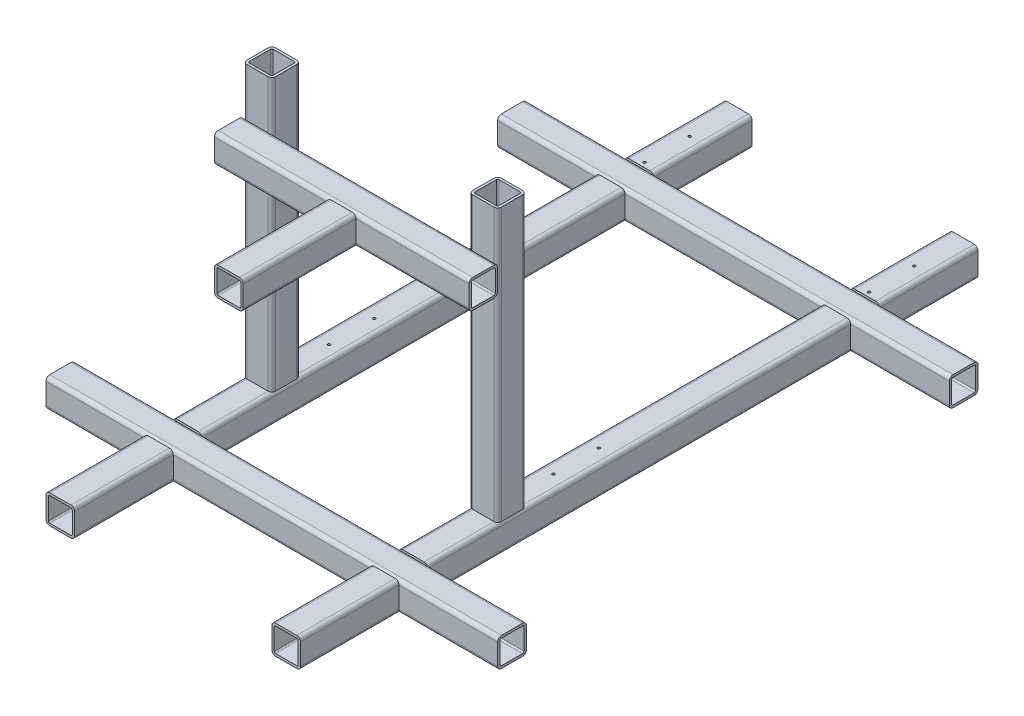
SolidWorks part; units mm, degrees
ref_plane "Front Plane" through (0, 0, 0) normal (0, 0, 1) x (1, 0, 0)
ref_plane "Top Plane" through (0, 0, 0) normal (0, 1, 0) x (1, 0, 0)
ref_plane "Right Plane" through (0, 0, 0) normal (1, 0, 0) x (0, 0, -1)
ref_plane "Bottom Face" through (0, 0, 0) normal (0, 1, 0) x (1, 0, 0)
ref_plane "Top Face" through (0, 38.1, 0) normal (0, 1, 0) x (1, 0, 0)
ref_plane "Mid Plane" through (0, 19.05, 0) normal (0, 1, 0) x (1, 0, 0)
ref_plane "Front Face" through (0, 0, 450) normal (0, 0, 1) x (1, 0, 0)
ref_plane "Back Face" through (0, 0, -450) normal (0, 0, 1) x (1, 0, 0)
ref_plane "Left Face" through (300, 0, 0) normal (1, 0, 0) x (0, 0, -1)
ref_plane "Right Face" through (-300, 0, 0) normal (1, 0, 0) x (0, 0, -1)
ref_plane "Divider Plane" through (0, 0, 150) normal (0, 0, 1) x (1, 0, 0)
ref_plane "Max Height Plane" through (0, 400, 0) normal (0, 1, 0) x (1, 0, 0)
ref_plane "Electronics Box Plane" through (0, 338.1, 0) normal (0, 1, 0) x (1, 0, 0)
sketch "Sketch2" plane through (300, 0, 0) normal (1, 0, 0) x (0, 0, -1)
  line L0 (330, 38.1) -> (-330, 38.1) construction
  line L5 (330, 0) -> (-330, 0) construction
  line L6 (0, 220) -> (0, -220) construction
  line L7 (-314.05, 38.1) -> (-285.95, 38.1)
  line L8 (-280.95, 33.1) -> (-280.95, 5)
  line L9 (-315.875, 33.1) -> (-315.875, 5)
  line L10 (-314.05, 3.175) -> (-285.95, 3.175)
  line L11 (-285.95, 0) -> (-314.05, 0)
  line L12 (-319.05, 5) -> (-319.05, 33.1)
  line L13 (-300, 38.1) -> (-300, 0) construction
  line L14 (-319.05, 19.05) -> (-280.95, 19.05) construction
  line L15 (-284.125, 5) -> (-284.125, 33.1)
  line L16 (-285.95, 34.925) -> (-314.05, 34.925)
  line L17 (-300, 34.925) -> (-300, 3.175) construction
  line L18 (-315.875, 19.05) -> (-284.125, 19.05) construction
  arc A0 (-285.95, 38.1) -> (-280.95, 33.1) centre (-285.95, 33.1) cw
  arc A1 (-280.95, 5) -> (-285.95, 0) centre (-285.95, 5) cw
  arc A2 (-314.05, 0) -> (-319.05, 5) centre (-314.05, 5) cw
  arc A3 (-319.05, 33.1) -> (-314.05, 38.1) centre (-314.05, 33.1) cw
  arc A4 (-315.875, 5) -> (-314.05, 3.175) centre (-314.05, 5) ccw
  arc A5 (-285.95, 3.175) -> (-284.125, 5) centre (-285.95, 5) ccw
  arc A6 (-284.125, 33.1) -> (-285.95, 34.925) centre (-285.95, 33.1) ccw
  arc A7 (-314.05, 34.925) -> (-315.875, 33.1) centre (-314.05, 33.1) ccw
  point P20 (-300, 19.05)
  point P39 (-300, 19.05)
  dimension "D1" = 5
  dimension "D2" = 300
  dimension "D3" = 3.175
extrude "Front Cross-Car Member" add sketch "Sketch2" against normal up to surface (600 mm away) up to plane "Right Face"
sketch "Sketch5" plane through (300, 0, 0) normal (1, 0, 0) x (0, 0, -1)
  line L0 (285.95, 38.1) -> (314.05, 38.1)
  line L1 (319.05, 33.1) -> (319.05, 5)
  line L2 (314.05, 0) -> (285.95, 0)
  line L3 (280.95, 5) -> (280.95, 33.1)
  line L4 (300, 38.1) -> (300, 0) construction
  line L5 (280.95, 19.05) -> (319.05, 19.05) construction
  line L6 (285.95, 34.925) -> (314.05, 34.925)
  line L7 (315.875, 33.1) -> (315.875, 5)
  line L8 (314.05, 3.175) -> (285.95, 3.175)
  line L9 (284.125, 5) -> (284.125, 33.1)
  line L10 (300, 34.925) -> (300, 3.175) construction
  line L11 (284.125, 19.05) -> (315.875, 19.05) construction
  line L12 (330, 0) -> (-330, 0) construction
  line L14 (330, 38.1) -> (-330, 38.1) construction
  line L15 (0, 220) -> (0, -220) construction
  arc A0 (314.05, 38.1) -> (319.05, 33.1) centre (314.05, 33.1) cw
  arc A1 (319.05, 5) -> (314.05, 0) centre (314.05, 5) cw
  arc A2 (285.95, 0) -> (280.95, 5) centre (285.95, 5) cw
  arc A3 (280.95, 33.1) -> (285.95, 38.1) centre (285.95, 33.1) cw
  arc A4 (314.05, 34.925) -> (315.875, 33.1) centre (314.05, 33.1) cw
  arc A5 (315.875, 5) -> (314.05, 3.175) centre (314.05, 5) cw
  arc A6 (285.95, 3.175) -> (284.125, 5) centre (285.95, 5) cw
  arc A7 (284.125, 33.1) -> (285.95, 34.925) centre (285.95, 33.1) cw
  point P32 (300, 19.05)
  point P33 (300, 19.05)
  dimension "D2" = 5
  dimension "D1" = 3.175
  dimension "D3" = 300
extrude "Back Cross-Car Member" add sketch "Sketch5" against normal up to surface (600 mm away) separate body up to plane "Right Face"
sketch "Sketch6" plane through (0, 0, -450) normal (0, 0, 1) x (1, 0, 0)
  line L0 (135.95, 38.1) -> (164.05, 38.1)
  line L1 (169.05, 33.1) -> (169.05, 5)
  line L2 (134.125, 33.1) -> (134.125, 5)
  line L3 (135.95, 3.175) -> (164.05, 3.175)
  line L4 (164.05, 0) -> (135.95, 0)
  line L5 (130.95, 5) -> (130.95, 33.1)
  line L6 (150, 38.1) -> (150, 0) construction
  line L7 (130.95, 19.05) -> (169.05, 19.05) construction
  line L8 (165.875, 5) -> (165.875, 33.1)
  line L9 (164.05, 34.925) -> (135.95, 34.925)
  line L10 (150, 34.925) -> (150, 3.175) construction
  line L11 (134.125, 19.05) -> (165.875, 19.05) construction
  line L12 (330, 38.1) -> (-330, 38.1) construction
  line L13 (330, 0) -> (-330, 0) construction
  line L14 (0, -220) -> (0, 220) construction
  arc A0 (164.05, 38.1) -> (169.05, 33.1) centre (164.05, 33.1) cw
  arc A1 (169.05, 5) -> (164.05, 0) centre (164.05, 5) cw
  arc A2 (135.95, 0) -> (130.95, 5) centre (135.95, 5) cw
  arc A3 (130.95, 33.1) -> (135.95, 38.1) centre (135.95, 33.1) cw
  arc A4 (134.125, 5) -> (135.95, 3.175) centre (135.95, 5) ccw
  arc A5 (164.05, 3.175) -> (165.875, 5) centre (164.05, 5) ccw
  arc A6 (165.875, 33.1) -> (164.05, 34.925) centre (164.05, 33.1) ccw
  arc A7 (135.95, 34.925) -> (134.125, 33.1) centre (135.95, 33.1) ccw
  point P16 (150, 19.05)
  point P33 (150, 19.05)
  dimension "D1" = 5
  dimension "D2" = 3.175
  dimension "D3" = 150
extrude "Back Left Along-Car Member" add sketch "Sketch6" along normal blind 130.95
extrude "Middle Left Along-Car Member" add sketch "Sketch6<2>" along normal blind 561.9 from offset 169.05
sketch "Sketch6<2>" plane through (0, 0, -450) normal (0, 0, 1) x (1, 0, 0) same geometry as "Sketch6"
extrude "Front Left Along-Car Member" add sketch "Sketch6<3>" along normal blind 130.95 from offset 769.05
sketch "Sketch6<3>" plane through (0, 0, -450) normal (0, 0, 1) x (1, 0, 0) same geometry as "Sketch6"
sketch "Sketch7" plane through (0, 0, -450) normal (0, 0, 1) x (1, 0, 0)
  line L0 (-164.05, 38.1) -> (-135.95, 38.1)
  line L1 (-130.95, 33.1) -> (-130.95, 5)
  line L2 (-165.875, 33.1) -> (-165.875, 5)
  line L3 (-164.05, 3.175) -> (-135.95, 3.175)
  line L4 (-135.95, 0) -> (-164.05, 0)
  line L5 (-169.05, 5) -> (-169.05, 33.1)
  line L6 (-150, 38.1) -> (-150, 0) construction
  line L7 (-169.05, 19.05) -> (-130.95, 19.05) construction
  line L8 (-134.125, 5) -> (-134.125, 33.1)
  line L9 (-135.95, 34.925) -> (-164.05, 34.925)
  line L10 (-150, 34.925) -> (-150, 3.175) construction
  line L11 (-165.875, 19.05) -> (-134.125, 19.05) construction
  line L12 (330, 38.1) -> (-330, 38.1) construction
  line L13 (330, 0) -> (-330, 0) construction
  line L14 (0, -220) -> (0, 220) construction
  arc A0 (-135.95, 38.1) -> (-130.95, 33.1) centre (-135.95, 33.1) cw
  arc A1 (-130.95, 5) -> (-135.95, 0) centre (-135.95, 5) cw
  arc A2 (-164.05, 0) -> (-169.05, 5) centre (-164.05, 5) cw
  arc A3 (-169.05, 33.1) -> (-164.05, 38.1) centre (-164.05, 33.1) cw
  arc A4 (-165.875, 5) -> (-164.05, 3.175) centre (-164.05, 5) ccw
  arc A5 (-135.95, 3.175) -> (-134.125, 5) centre (-135.95, 5) ccw
  arc A6 (-134.125, 33.1) -> (-135.95, 34.925) centre (-135.95, 33.1) ccw
  arc A7 (-164.05, 34.925) -> (-165.875, 33.1) centre (-164.05, 33.1) ccw
  point P16 (-150, 19.05)
  point P33 (-150, 19.05)
  dimension "D1" = 5
  dimension "D2" = 3.175
  dimension "D3" = 150
extrude "Back Right Along-Car Member" add sketch "Sketch7" along normal blind 130.95
extrude "Middle Right Along-Car Member" add sketch "Sketch7<2>" along normal blind 561.9 from offset 169.05
sketch "Sketch7<2>" plane through (0, 0, -450) normal (0, 0, 1) x (1, 0, 0) same geometry as "Sketch7"
extrude "Front Right Along-Car Member" add sketch "Sketch7<3>" along normal blind 130.95 from offset 769.05
sketch "Sketch7<3>" plane through (0, 0, -450) normal (0, 0, 1) x (1, 0, 0) same geometry as "Sketch7"
sketch "Sketch8" plane through (0, 38.1, 0) normal (0, 1, 0) x (1, 0, 0)
  line L0 (-164.05, -150) -> (-135.95, -150)
  line L1 (-130.95, -155) -> (-130.95, -183.1)
  line L2 (-165.875, -155) -> (-165.875, -183.1)
  line L3 (-164.05, -184.925) -> (-135.95, -184.925)
  line L4 (-135.95, -188.1) -> (-164.05, -188.1)
  line L5 (-169.05, -183.1) -> (-169.05, -155)
  line L6 (-150, -150) -> (-150, -188.1) construction
  line L7 (-169.05, -169.05) -> (-130.95, -169.05) construction
  line L8 (-134.125, -183.1) -> (-134.125, -155)
  line L9 (-135.95, -153.175) -> (-164.05, -153.175)
  line L10 (-150, -153.175) -> (-150, -184.925) construction
  line L11 (-165.875, -169.05) -> (-134.125, -169.05) construction
  line L12 (-220, -150) -> (220, -150) construction
  line L13 (0, -220) -> (0, 220) construction
  arc A0 (-135.95, -150) -> (-130.95, -155) centre (-135.95, -155) cw
  arc A1 (-130.95, -183.1) -> (-135.95, -188.1) centre (-135.95, -183.1) cw
  arc A2 (-164.05, -188.1) -> (-169.05, -183.1) centre (-164.05, -183.1) cw
  arc A3 (-169.05, -155) -> (-164.05, -150) centre (-164.05, -155) cw
  arc A4 (-165.875, -183.1) -> (-164.05, -184.925) centre (-164.05, -183.1) ccw
  arc A5 (-135.95, -184.925) -> (-134.125, -183.1) centre (-135.95, -183.1) ccw
  arc A6 (-134.125, -155) -> (-135.95, -153.175) centre (-135.95, -155) ccw
  arc A7 (-164.05, -153.175) -> (-165.875, -155) centre (-164.05, -155) ccw
  point P16 (-150, -169.05)
  point P33 (-150, -169.05)
  dimension "D1" = 5
  dimension "D2" = 3.175
  dimension "D3" = 38.1
  dimension "D4" = 150
extrude "Right Vertical Member" add sketch "Sketch8" along normal up to surface (361.9 mm away) up to plane "Max Height Plane"
sketch "Sketch10" plane through (0, 38.1, 0) normal (0, 1, 0) x (1, 0, 0)
  line L0 (135.95, -150) -> (164.05, -150)
  line L1 (169.05, -155) -> (169.05, -183.1)
  line L2 (134.125, -155) -> (134.125, -183.1)
  line L3 (135.95, -184.925) -> (164.05, -184.925)
  line L4 (164.05, -188.1) -> (135.95, -188.1)
  line L5 (130.95, -183.1) -> (130.95, -155)
  line L6 (150, -150) -> (150, -188.1) construction
  line L7 (130.95, -169.05) -> (169.05, -169.05) construction
  line L8 (165.875, -183.1) -> (165.875, -155)
  line L9 (164.05, -153.175) -> (135.95, -153.175)
  line L10 (150, -153.175) -> (150, -184.925) construction
  line L11 (134.125, -169.05) -> (165.875, -169.05) construction
  line L12 (-220, -150) -> (220, -150) construction
  line L13 (0, -220) -> (0, 220) construction
  arc A0 (164.05, -150) -> (169.05, -155) centre (164.05, -155) cw
  arc A1 (169.05, -183.1) -> (164.05, -188.1) centre (164.05, -183.1) cw
  arc A2 (135.95, -188.1) -> (130.95, -183.1) centre (135.95, -183.1) cw
  arc A3 (130.95, -155) -> (135.95, -150) centre (135.95, -155) cw
  arc A4 (134.125, -183.1) -> (135.95, -184.925) centre (135.95, -183.1) ccw
  arc A5 (164.05, -184.925) -> (165.875, -183.1) centre (164.05, -183.1) ccw
  arc A6 (165.875, -155) -> (164.05, -153.175) centre (164.05, -155) ccw
  arc A7 (135.95, -153.175) -> (134.125, -155) centre (135.95, -155) ccw
  point P16 (150, -169.05)
  point P33 (150, -169.05)
  dimension "D1" = 5
  dimension "D2" = 3.175
  dimension "D3" = 38.1
  dimension "D4" = 150
extrude "Left Vertical Member" add sketch "Sketch10" along normal up to surface (361.9 mm away) up to plane "Max Height Plane"
sketch "Sketch11" plane through (300, 0, 0) normal (1, 0, 0) x (0, 0, -1)
  line L0 (-221.2, 338.1) -> (-193.1, 338.1)
  line L1 (-188.1, 333.1) -> (-188.1, 305)
  line L2 (-223.025, 333.1) -> (-223.025, 305)
  line L3 (-221.2, 303.175) -> (-193.1, 303.175)
  line L4 (-193.1, 300) -> (-221.2, 300)
  line L5 (-226.2, 305) -> (-226.2, 333.1)
  line L6 (-207.15, 338.1) -> (-207.15, 300) construction
  line L7 (-226.2, 319.05) -> (-188.1, 319.05) construction
  line L8 (-191.275, 305) -> (-191.275, 333.1)
  line L9 (-193.1, 334.925) -> (-221.2, 334.925)
  line L10 (-207.15, 334.925) -> (-207.15, 303.175) construction
  line L11 (-223.025, 319.05) -> (-191.275, 319.05) construction
  line L12 (-150, 220) -> (-150, -220) construction
  line L13 (330, 338.1) -> (-330, 338.1) construction
  arc A0 (-193.1, 338.1) -> (-188.1, 333.1) centre (-193.1, 333.1) cw
  arc A1 (-188.1, 305) -> (-193.1, 300) centre (-193.1, 305) cw
  arc A2 (-221.2, 300) -> (-226.2, 305) centre (-221.2, 305) cw
  arc A3 (-226.2, 333.1) -> (-221.2, 338.1) centre (-221.2, 333.1) cw
  arc A4 (-223.025, 305) -> (-221.2, 303.175) centre (-221.2, 305) ccw
  arc A5 (-193.1, 303.175) -> (-191.275, 305) centre (-193.1, 305) ccw
  arc A6 (-191.275, 333.1) -> (-193.1, 334.925) centre (-193.1, 333.1) ccw
  arc A7 (-221.2, 334.925) -> (-223.025, 333.1) centre (-221.2, 333.1) ccw
  point P16 (-207.15, 319.05)
  point P33 (-207.15, 319.05)
  dimension "D1" = 5
  dimension "D2" = 3.175
  dimension "D3" = 38.1
  dimension "D4" = 38.1
extrude "Upper Cross-Car Member" add sketch "Sketch11" against normal blind 338.1 from offset 130.95 offset against normal yes
sketch "Sketch12" plane through (0, 0, 150) normal (0, 0, 1) x (1, 0, 0)
  line L0 (-14.05, 338.1) -> (14.05, 338.1)
  line L1 (19.05, 333.1) -> (19.05, 305)
  line L2 (-15.875, 333.1) -> (-15.875, 305)
  line L3 (-14.05, 303.175) -> (14.05, 303.175)
  line L4 (14.05, 300) -> (-14.05, 300)
  line L5 (-19.05, 305) -> (-19.05, 333.1)
  line L6 (0, 338.1) -> (0, 300) construction
  line L7 (-19.05, 319.05) -> (19.05, 319.05) construction
  line L8 (15.875, 305) -> (15.875, 333.1)
  line L9 (14.05, 334.925) -> (-14.05, 334.925)
  line L10 (0, 334.925) -> (0, 303.175) construction
  line L11 (-15.875, 319.05) -> (15.875, 319.05) construction
  line L12 (330, 338.1) -> (-330, 338.1) construction
  line L13 (0, -220) -> (0, 220) construction
  arc A0 (14.05, 338.1) -> (19.05, 333.1) centre (14.05, 333.1) cw
  arc A1 (19.05, 305) -> (14.05, 300) centre (14.05, 305) cw
  arc A2 (-14.05, 300) -> (-19.05, 305) centre (-14.05, 305) cw
  arc A3 (-19.05, 333.1) -> (-14.05, 338.1) centre (-14.05, 333.1) cw
  arc A4 (-15.875, 305) -> (-14.05, 303.175) centre (-14.05, 305) ccw
  arc A5 (14.05, 303.175) -> (15.875, 305) centre (14.05, 305) ccw
  arc A6 (15.875, 333.1) -> (14.05, 334.925) centre (14.05, 333.1) ccw
  arc A7 (-14.05, 334.925) -> (-15.875, 333.1) centre (-14.05, 333.1) ccw
  point P16 (0, 319.05)
  point P33 (0, 319.05)
  dimension "D1" = 5
  dimension "D2" = 3.175
  dimension "D3" = 38.1
extrude "E-Box Platform Base" add sketch "Sketch12" along normal blind 150 from offset 76.2
sketch "Water Tank Mount Holes" plane through (0, 38.1, 0) normal (0, 1, 0) x (1, 0, 0)
  point P0 (-149.13, -93.95)
  point P1 (-149.13, -33.95)
  point P3 (149.13, -93.95)
  point P4 (149.13, -33.95)
  point P5 (149.13, 325.13)
  point P9 (149.13, 385.13)
  point P11 (-149.13, 325.13)
  point P13 (-149.13, 385.13)
hole_wizard "M3 Clearance Hole2" positions "Sketch14" profile "Sketch15" hole size "M3" standard "ANSI Metric" end condition through all
sketch "Sketch14" plane through (0, 38.1, 0) normal (0, 1, 0) x (1, 0, 0)
  point P0 (-149.13, -33.95)
  point P3 (-149.13, -93.95)
  point P6 (149.13, -93.95)
  point P9 (149.13, -33.95)
  point P12 (149.13, 325.13)
  point P15 (149.13, 385.13)
  point P18 (-149.13, 385.13)
  point P21 (-149.13, 325.13)
sketch "Sketch15" plane through (-149.13, 38.1, 33.95) normal (1, 0, 0) x (0, 0, 1)
  line L0 (0, 0) -> (0, 38.1)
  line L1 (0, 38.1) -> (1.7, 38.1)
  line L2 (1.7, 38.1) -> (1.7, 0)
  line L5 (1.7, 0) -> (0, 0)
  line L11 (0, -6.35) -> (0, 107.95) construction
  dimension "Thru Hole Dia." = 3.4
  dimension "Thru Hole Depth" = 38.1
equation "\"D1@Front Face\" = \"frameLength@Master Assembly.SLDASM\" / 2"
equation "\"D1@Back Face\" = \"frameLength@Master Assembly.SLDASM\" / 2"
equation "\"D1@Left Face\"=\"frameWidth@Master Assembly.SLDASM\"/2"
equation "\"D1@Right Face\" = \"frameWidth@Master Assembly.SLDASM\" / 2"
equation "\"D1@Top Face\"=\"frameTubeStockHeight@Master Assembly.SLDASM\""
equation "\"D2@Sketch2\"=\"frameMemberDistLength@Master Assembly.SLDASM\"/2"
equation "\"D3@Sketch2\"=\"frameTubeStockWallThickness@Master Assembly.SLDASM\""
equation "\"D1@Sketch5\"=\"frameTubeStockWallThickness@Master Assembly.SLDASM\""
equation "\"D3@Sketch5\"=\"frameMemberDistLength@Master Assembly.SLDASM\"/2"
equation "\"D3@Sketch6\"=\"frameMemberDistWidth@Master Assembly.SLDASM\"/2"
equation "\"D1@Back Left Along-Car Member\"=(\"frameLength@Master Assembly.SLDASM\" - \"frameMemberDistLength@Master Assembly.SLDASM\" - \"frameTubeStockHeight@Master Assembly.SLDASM\")  / 2"
equation "\"D19@Middle Left Along-Car Member\" = ( \"frameLength@Master Assembly.SLDASM\" - \"frameMemberDistLength@Master Assembly.SLDASM\" + \"frameTubeStockHeight@Master Assembly.SLDASM\" ) / 2"
equation "\"D1@Middle Left Along-Car Member\"=\"frameMemberDistLength@Master Assembly.SLDASM\" - \"frameTubeStockHeight@Master Assembly.SLDASM\""
equation "\"D19@Front Left Along-Car Member\"=( \"frameLength@Master Assembly.SLDASM\" - \"frameMemberDistLength@Master Assembly.SLDASM\" )  / 2 + \"frameMemberDistLength@Master Assembly.SLDASM\" + \"frameTubeStockHeight@Master Assembly.SLDASM\" / 2"
equation "\"D1@Front Left Along-Car Member\"=(\"frameLength@Master Assembly.SLDASM\" - \"frameMemberDistLength@Master Assembly.SLDASM\" - \"frameTubeStockHeight@Master Assembly.SLDASM\")  / 2"
equation "\"D3@Sketch7\"=\"frameMemberDistWidth@Master Assembly.SLDASM\"/2"
equation "\"D1@Back Right Along-Car Member\"=(\"frameLength@Master Assembly.SLDASM\" - \"frameMemberDistLength@Master Assembly.SLDASM\" - \"frameTubeStockHeight@Master Assembly.SLDASM\")  / 2"
equation "\"D19@Middle Right Along-Car Member\" = ( \"frameLength@Master Assembly.SLDASM\" - \"frameMemberDistLength@Master Assembly.SLDASM\" + \"frameTubeStockHeight@Master Assembly.SLDASM\" ) / 2"
equation "\"D1@Middle Right Along-Car Member\"=\"frameMemberDistLength@Master Assembly.SLDASM\" - \"frameTubeStockHeight@Master Assembly.SLDASM\""
equation "\"D19@Front Right Along-Car Member\"=( \"frameLength@Master Assembly.SLDASM\" - \"frameMemberDistLength@Master Assembly.SLDASM\" )  / 2 + \"frameMemberDistLength@Master Assembly.SLDASM\" + \"frameTubeStockHeight@Master Assembly.SLDASM\" / 2"
equation "\"D1@Front Right Along-Car Member\"=(\"frameLength@Master Assembly.SLDASM\" - \"frameMemberDistLength@Master Assembly.SLDASM\" - \"frameTubeStockHeight@Master Assembly.SLDASM\")  / 2"
equation "\"D1@Divider Plane\"= \"frameDividerPlaneOffset@Master Assembly.SLDASM\""
equation "\"D3@Sketch8\"=\"frameTubeStockHeight@Master Assembly.SLDASM\""
equation "\"D4@Sketch8\"=\"frameMemberDistWidth@Master Assembly.SLDASM\"/2"
equation "\"D1@Max Height Plane\" = \"frameHeight@Master Assembly.SLDASM\""
equation "\"D4@Sketch10\"=\"frameMemberDistWidth@Master Assembly.SLDASM\"/2"
equation "\"D1@Electronics Box Plane\" = \"eboxPlaneHeight@Master Assembly.SLDASM\""
equation "\"D4@Sketch11\"=\"frameTubeStockHeight@Master Assembly.SLDASM\""
equation "\"D19@Upper Cross-Car Member\" = ( \"frameWidth@Master Assembly.SLDASM\" - \"frameMemberDistWidth@Master Assembly.SLDASM\" - \"frameTubeStockHeight@Master Assembly.SLDASM\" ) / 2"
equation "\"D1@Upper Cross-Car Member\" = \"frameMemberDistWidth@Master Assembly.SLDASM\" + \"frameTubeStockHeight@Master Assembly.SLDASM\""
equation "\"D19@E-Box Platform Base\"= \"frameTubeStockHeight@Master Assembly.SLDASM\" * 2"
equation "\"D2@Sketch6\"=\"frameTubeStockWallThickness@Master Assembly.SLDASM\""
equation "\"D2@Sketch7\"=\"frameTubeStockWallThickness@Master Assembly.SLDASM\""
equation "\"D2@Sketch8\"=\"frameTubeStockWallThickness@Master Assembly.SLDASM\""
equation "\"D3@Sketch10\"=\"frameTubeStockHeight@Master Assembly.SLDASM\""
equation "\"D2@Sketch10\"=\"frameTubeStockWallThickness@Master Assembly.SLDASM\""
equation "\"D3@Sketch11\"=\"frameTubeStockHeight@Master Assembly.SLDASM\""
equation "\"D2@Sketch11\"=\"frameTubeStockWallThickness@Master Assembly.SLDASM\""
equation "\"D3@Sketch12\"=\"frameTubeStockHeight@Master Assembly.SLDASM\""
equation "\"D2@Sketch12\"=\"frameTubeStockWallThickness@Master Assembly.SLDASM\""
